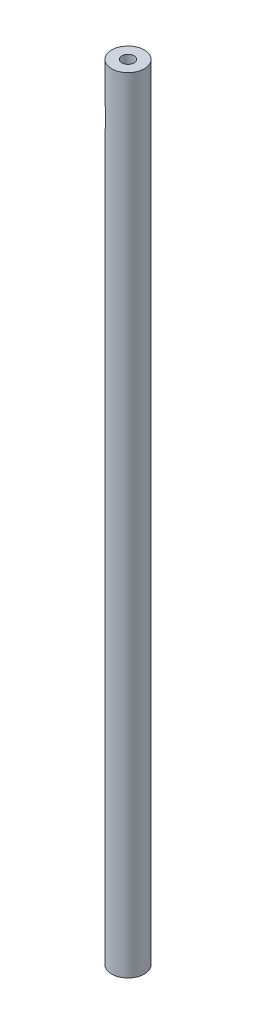
SolidWorks part; units mm, degrees
material "Cast Carbon Steel"
ref_plane "Front Plane" through (0, 0, 0) normal (0, 0, 1) x (1, 0, 0)
ref_plane "Top Plane" through (0, 0, 0) normal (0, 1, 0) x (1, 0, 0)
ref_plane "Right Plane" through (0, 0, 0) normal (1, 0, 0) x (0, 0, -1)
sketch "Sketch1" plane through (0, 0, 0) normal (0, 1, 0) x (1, 0, 0)
  circle A0 centre (0, 0) radius 12.7
  circle A1 centre (0, 0) radius 4.7625
  dimension "D1" = 25.4
  dimension "D2" = 7.9375
extrude "Boss-Extrude1" add sketch "Sketch1" along normal blind 609.6
ref_plane "Plane1" through (0, 0, 0) normal (0, -1, 0) x (-1, 0, 0)
ref_plane "Plane2" through (-12.7, 0, 0) normal (-1, 0, 0) x (0, 0, 1)
sketch "Sketch3" plane through (-12.7, 0, 0) normal (-1, 0, 0) x (0, 0, 1)
  line L0 (-12.7, 0) -> (12.7, 0) construction
  circle A0 centre (0, 571.754) radius 12.7
  dimension "D1" = 25.4
  dimension "D2" = 571.754
extrude "Cut-Extrude1" cut sketch "Sketch3" against normal blind 6.35
